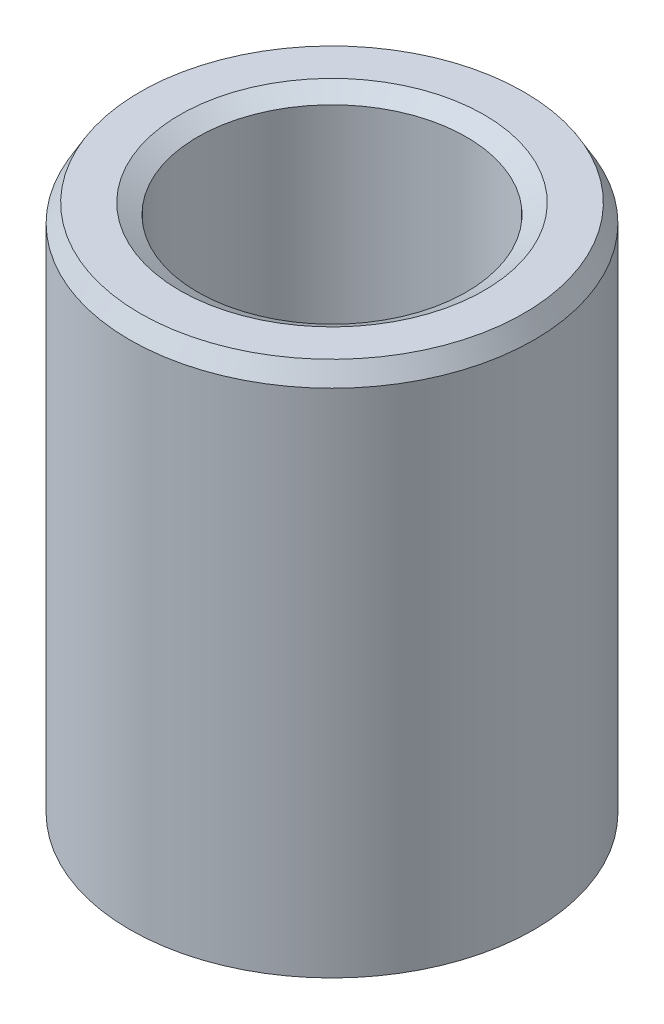
SolidWorks part; units mm, degrees
ref_plane "Front Plane" through (0, 0, 0) normal (0, 0, 1) x (1, 0, 0)
ref_plane "Top Plane" through (0, 0, 0) normal (0, 1, 0) x (1, 0, 0)
ref_plane "Right Plane" through (0, 0, 0) normal (1, 0, 0) x (0, 0, -1)
sketch "Sketch1" plane through (0, 0, 0) normal (0, 1, 0) x (1, 0, 0)
  circle A0 centre (0, 0) radius 10
  dimension "SLEEVE_OD" = 20
extrude "Boss-Extrude1" add sketch "Sketch1" along normal blind 26.6514
sketch "Sketch2" plane through (0, 0, 0) normal (0, 1, 0) x (1, 0, 0)
  circle A0 centre (0, 0) radius 6.6478
  dimension "BORE_D" = 13.2957
extrude "Cut-Extrude1" cut sketch "Sketch2" along normal through all
chamfer "Chamfer1" distance 0.8809 angle 30 4 edges at (0, 26.6514, 6.6478) (0, 0, 6.6478) (0, 0, 10) (0, 26.6514, 10) first distance on face at (0, 26.6514, 6.6478) first distance on face at (0, 0, 6.6478) first distance on face at (0, 26.6514, 10)
